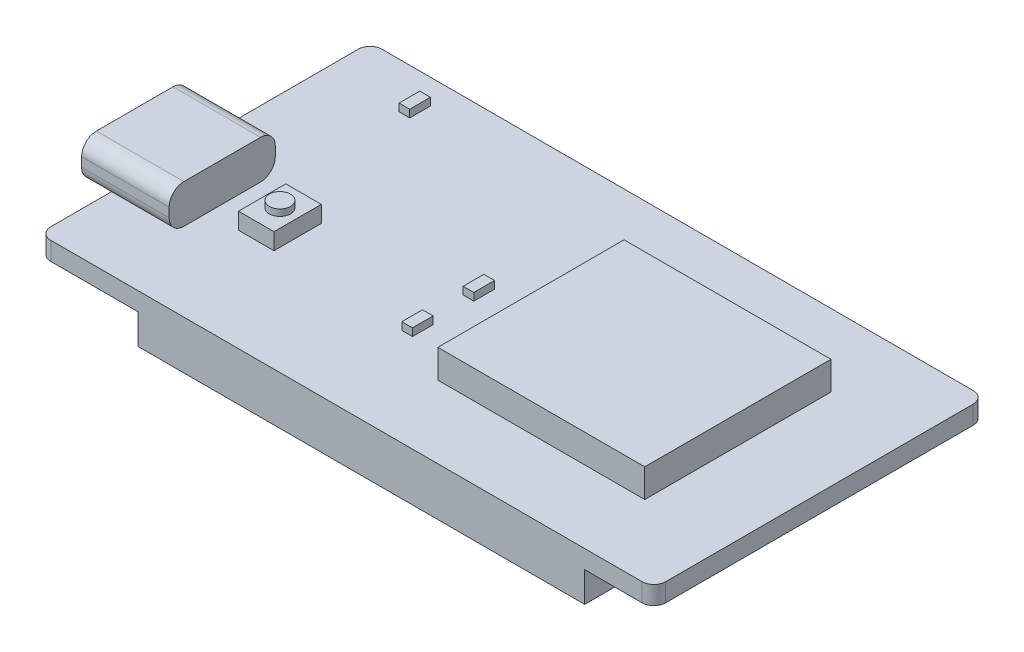
SolidWorks part; units mm, degrees
ref_plane "前基準面" through (0, 0, 0) normal (0, 0, 1) x (1, 0, 0)
ref_plane "上基準面" through (0, 0, 0) normal (0, 1, 0) x (1, 0, 0)
ref_plane "右基準面" through (0, 0, 0) normal (1, 0, 0) x (0, 0, -1)
sketch "草圖1" plane through (0, 0, 0) normal (0, 1, 0) x (1, 0, 0)
  line L1 (-26, 14) -> (26, 14)
  line L2 (-26, 14) -> (-26, -14)
  line L3 (-26, -14) -> (26, -14)
  line L4 (26, 14) -> (26, -14)
  line L5 (-26, 14) -> (26, -14) construction
  line L6 (-26, -14) -> (26, 14) construction
  point P0 (0, 0)
  dimension "D1" = 28
  dimension "D2" = 52
extrude "填料-伸長1" add sketch "草圖1" along normal blind 1.55
fillet "圓角1" radius 1 4 edges at (26, 0.775, -14) (-26, 0.775, -14) (-26, 0.775, 14) (26, 0.775, 14)
sketch "草圖2" plane through (0, 0, 0) normal (0, -1, 0) x (1, 0, 0)
  line L0 (-25, 14) -> (25, 14) construction
  line L1 (-17.61, 14) -> (20.15, 14)
  line L2 (-17.61, 14) -> (-17.61, 11.46)
  line L3 (-17.61, 11.46) -> (20.15, 11.46)
  line L4 (20.15, 14) -> (20.15, 11.46)
  line L5 (26, 13) -> (26, -13) construction
  line L6 (-26, 0) -> (26, 0) construction
  line L7 (-26, -13) -> (-26, 13) construction
  line L8 (20.15, -14) -> (20.15, -11.46)
  line L9 (-17.61, -14) -> (-17.61, -11.46)
  line L10 (-17.61, -14) -> (20.15, -14)
  line L11 (-17.61, -11.46) -> (20.15, -11.46)
  dimension "D1" = 2.54
  dimension "D2" = 37.76
  dimension "D3" = 5.85
extrude "填料-伸長2" add sketch "草圖2" along normal blind 2.54
sketch "草圖3" plane through (0, 1.55, 0) normal (0, 1, 0) x (1, 0, 0)
  line L0 (26, -13) -> (26, 13) construction
  line L1 (1.6, 7.875) -> (19.1, 7.875)
  line L2 (1.6, 7.875) -> (1.6, -7.875)
  line L3 (1.6, -7.875) -> (19.1, -7.875)
  line L4 (19.1, 7.875) -> (19.1, -7.875)
  line L5 (1.6, 7.875) -> (19.1, -7.875) construction
  line L6 (1.6, -7.875) -> (19.1, 7.875) construction
  point P0 (10.35, 0)
  dimension "D1" = 17.5
  dimension "D2" = 15.75
  dimension "D3" = 6.9
extrude "填料-伸長4" add sketch "草圖3" along normal blind 2.4
sketch "草圖5" plane through (-26, 0, 0) normal (-1, 0, 0) x (0, 0, 1)
  line L0 (-13, 1.55) -> (13, 1.55) construction
  line L1 (7.35, 1.55) -> (0.87, 1.55)
  line L2 (8.6, 2.8) -> (8.6, 3.58)
  line L3 (7.35, 4.83) -> (0.87, 4.83)
  line L4 (-0.38, 2.8) -> (-0.38, 3.58)
  line L5 (-7.875, 1.55) -> (7.875, 1.55) construction
  line L6 (14, 1.55) -> (14, 0) construction
  line L7 (-0.38, 3.19) -> (8.6, 3.19) construction
  line L8 (4.11, 4.83) -> (4.11, 1.55) construction
  arc A0 (0.87, 4.83) -> (-0.38, 3.58) centre (0.87, 3.58) ccw
  arc A1 (0.87, 1.55) -> (-0.38, 2.8) centre (0.87, 2.8) cw
  arc A2 (7.35, 1.55) -> (8.6, 2.8) centre (7.35, 2.8) ccw
  arc A3 (8.6, 3.58) -> (7.35, 4.83) centre (7.35, 3.58) ccw
  point P13 (-0.38, 4.83)
  point P16 (-0.38, 1.55)
  point P19 (8.6, 1.55)
  point P22 (8.6, 4.83)
  point P26 (4.11, 3.19)
  dimension "D4" = 1.25
  dimension "D1" = 3.28
  dimension "D2" = 8.98
  dimension "D3" = 5.4
extrude "填料-伸長6" add sketch "草圖5" against normal blind 5.6 and the other way blind 1.8
sketch "Sketch1" plane through (0, 1.55, 0) normal (0, 1, 0) x (1, 0, 0)
  line L0 (25, 14) -> (-25, 14) construction
  line L1 (-17.8, -1.33) -> (-14.8, -1.33)
  line L2 (-17.8, -1.33) -> (-17.8, -5.33)
  line L3 (-17.8, -5.33) -> (-14.8, -5.33)
  line L4 (-14.8, -1.33) -> (-14.8, -5.33)
  line L5 (-17.8, -1.33) -> (-14.8, -5.33) construction
  line L6 (-17.8, -5.33) -> (-14.8, -1.33) construction
  line L8 (-26, 13) -> (-26, -0.87) construction
  circle A0 centre (-16.3, -3.33) radius 0.9
  point P0 (-16.3, -3.33)
  dimension "D5" = 1.8
  dimension "D1" = 15.33
  dimension "D2" = 3
  dimension "D3" = 8.2
  dimension "D4" = 4
extrude "Boss-Extrude1" add sketch "Sketch1" along normal blind 1.4 contours A0 | L4 L1 L2 L3 A0 region at (-16.3, 1.55, 1.38) region at (-16.3, 1.55, 3.33)
extrude "Boss-Extrude2" add sketch "Sketch1<4>" along normal blind 1.95 contours A0 region at (-16.3, 1.55, 3.33)
sketch "Sketch1<4>" plane through (0, 1.55, 0) normal (0, 1, 0) x (1, 0, 0) same geometry as "Sketch1"
sketch "Sketch2" plane through (0, 1.55, 0) normal (0, 1, 0) x (1, 0, 0)
  line L0 (25, 14) -> (-25, 14) construction
  line L1 (-19.69, 11.89) -> (-18.79, 11.89)
  line L2 (-19.69, 11.89) -> (-19.69, 10.14)
  line L3 (-19.69, 10.14) -> (-18.79, 10.14)
  line L4 (-18.79, 11.89) -> (-18.79, 10.14)
  line L5 (-19.69, 11.89) -> (-18.79, 10.14) construction
  line L6 (-19.69, 10.14) -> (-18.79, 11.89) construction
  line L7 (-26, 13) -> (-26, -0.87) construction
  line L8 (26, -13) -> (26, 13) construction
  line L9 (-3.56, 1.18) -> (-2.66, 1.18)
  line L10 (-3.56, 1.18) -> (-3.56, -0.57)
  line L11 (-3.56, -0.57) -> (-2.66, -0.57)
  line L12 (-2.66, 1.18) -> (-2.66, -0.57)
  line L13 (-3.56, 1.18) -> (-2.66, -0.57) construction
  line L14 (-3.56, -0.57) -> (-2.66, 1.18) construction
  line L15 (-25, -14) -> (25, -14) construction
  line L16 (-3.56, -4.01) -> (-2.66, -4.01)
  line L17 (-3.56, -4.01) -> (-3.56, -5.76)
  line L18 (-3.56, -5.76) -> (-2.66, -5.76)
  line L19 (-2.66, -4.01) -> (-2.66, -5.76)
  line L20 (-3.56, -4.01) -> (-2.66, -5.76) construction
  line L21 (-3.56, -5.76) -> (-2.66, -4.01) construction
  point P0 (-19.24, 11.015)
  point P9 (-3.11, 0.305)
  point P16 (-3.11, -4.885)
  point P21 (-3.0548, -3.9055)
  dimension "D1" = 0.9
  dimension "D2" = 1.75
  dimension "D3" = 2.11
  dimension "D4" = 6.31
  dimension "D5" = 0.9
  dimension "D6" = 1.75
  dimension "D7" = 12.82
  dimension "D8" = 28.66
  dimension "D9" = 8.24
  dimension "D10" = 0.9
  dimension "D11" = 1.75
extrude "Boss-Extrude3" add sketch "Sketch2" along normal blind 0.64
